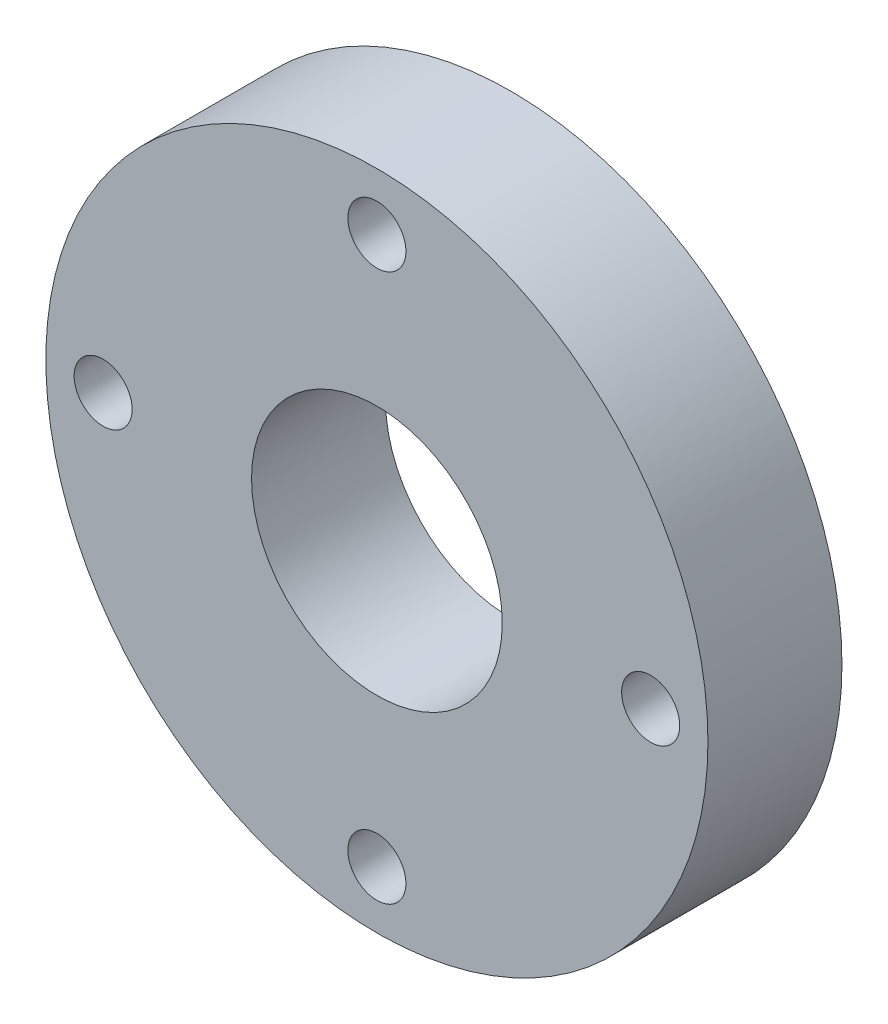
SolidWorks part; units mm, degrees
material "6061-T6 (SS)"
ref_plane "Front Plane" through (0, 0, 0) normal (0, 0, 1) x (1, 0, 0)
ref_plane "Top Plane" through (0, 0, 0) normal (0, 1, 0) x (1, 0, 0)
ref_plane "Right Plane" through (0, 0, 0) normal (1, 0, 0) x (0, 0, -1)
sketch "Sketch1" plane through (0, 0, 0) normal (1, 0, 0) x (0, 0, -1)
  line L0 (-95.847, -9.525) -> (-141.966, -9.525)
  line L5 (-1000, 0) -> (49000, 0)
  line L6 (0, -9.525) -> (0, 9.525)
  line L13 (0, 9.525) -> (-45.847, 9.525)
  line L26 (-45.847, 9.525) -> (-45.847, 12.7)
  line L27 (-45.847, 12.7) -> (-95.847, 12.7)
  line L32 (-95.847, 12.7) -> (-95.847, 9.525)
  line L34 (-160, 7) -> (-160, -7)
  line L36 (-95.847, -9.525) -> (-95.847, -12.7)
  line L37 (-95.847, -12.7) -> (-45.847, -12.7)
  line L38 (-45.847, -12.7) -> (-45.847, -9.525)
  line L39 (0, -9.525) -> (-45.847, -9.525)
  line L40 (-25.305, 37.6491) -> (-16.305, 37.6491)
  line L41 (-111.341, 22.6187) -> (-95.847, 22.6187)
  line L42 (-111.341, 22.6187) -> (-111.341, -22.6187)
  line L43 (-111.341, -22.6187) -> (-95.847, -22.6187)
  line L44 (-95.847, 22.6187) -> (-95.847, -22.6187)
  line L45 (-111.341, 22.6187) -> (-95.847, -22.6187) construction
  line L46 (-111.341, -22.6187) -> (-95.847, 22.6187) construction
  line L47 (-30.353, 22.6187) -> (-45.847, 22.6187)
  line L48 (-30.353, 22.6187) -> (-30.353, -22.6187)
  line L49 (-30.353, -22.6187) -> (-45.847, -22.6187)
  line L50 (-45.847, 22.6187) -> (-45.847, -22.6187)
  line L51 (-30.353, 22.6187) -> (-45.847, -22.6187) construction
  line L52 (-30.353, -22.6187) -> (-45.847, 22.6187) construction
  line L59 (-16.305, 37.6491) -> (-16.305, -37.6491)
  line L60 (-16.305, -37.6491) -> (-25.305, -37.6491)
  line L61 (-25.305, -22.6187) -> (-27.305, -22.6187)
  line L62 (-27.305, -22.6187) -> (-27.305, -12.5)
  line L63 (-27.305, -12.5) -> (-25.305, -12.5)
  line L64 (-25.305, -12.5) -> (-25.305, 12.5)
  line L65 (-25.305, 12.5) -> (-27.305, 12.5)
  line L66 (-27.305, 12.5) -> (-27.305, 22.6187)
  line L67 (-27.305, 22.6187) -> (-25.305, 22.6187)
  line L68 (-25.305, 22.6187) -> (-25.305, 37.6491)
  line L69 (-25.305, -22.6187) -> (-25.305, -37.6491)
  line L71 (-119.469, 37.6491) -> (-26.305, 37.6491)
  line L72 (-119.469, 37.6491) -> (-119.469, -37.6491)
  line L73 (-119.469, -37.6491) -> (-26.305, -37.6491)
  line L74 (-26.305, 37.6491) -> (-26.305, -37.6491)
  line L75 (-119.469, 37.6491) -> (-26.305, -37.6491) construction
  line L76 (-119.469, -37.6491) -> (-26.305, 37.6491) construction
  line L78 (-147.3, -7) -> (-160, -7)
  line L79 (-95.847, 9.525) -> (-141.966, 9.525)
  line L80 (-147.3, 7) -> (-160, 7)
  line L82 (-118.9065, 9.525) -> (-118.9065, -9.525) construction
  line L83 (-22.9235, 9.525) -> (-22.9235, -9.525) construction
  line L96 (-119.469, 37.6492) -> (-134.709, 37.6492)
  line L98 (-119.469, -37.6491) -> (-134.709, -37.6491)
  line L99 (-134.709, 37.6492) -> (-134.709, -37.6491)
  line L110 (-119.469, 37.6492) -> (-119.469, -37.6491)
  line L111 (-147.3, 7) -> (-147.3, 7.493)
  line L112 (-147.3, 7.493) -> (-141.966, 7.493)
  line L113 (-141.966, 7.493) -> (-141.966, 9.525)
  line L114 (-141.966, -9.525) -> (-141.966, -7.493)
  line L115 (-141.966, -7.493) -> (-147.3, -7.493)
  line L116 (-147.3, -7.493) -> (-147.3, -7)
  point P3 (0, 0)
  point P18 (-103.594, 0)
  point P24 (-38.1, 0)
  point P29 (-72.887, 0)
  point P48 (-16.305, 31.1339)
  point P70 (-134.709, 31.1339)
revolve "Main_body" add sketch "Sketch1" angle 360 about L5 region at (0, 23.5871, 127.089)
sketch "Sketch5" plane through (0, 0, 134.709) normal (0, 0, 1) x (1, 0, 0)
  circle A0 centre (0, 0) radius 14.2558
  dimension "D1" = 28.5115
extrude "seal_seat" cut sketch "Sketch5" against normal through all
hole_wizard "M6 Clearance Hole1" positions "Sketch3" profile "Sketch4" hole size "M6" standard "ANSI Metric" end condition through all
sketch "Sketch3" plane through (0, 0, 134.709) normal (0, 0, 1) x (1, 0, 0)
  point P0 (0, 31.1339)
sketch "Sketch4" plane through (0, 31.1339, 134.709) normal (1, 0, 0) x (0, -1, 0)
  line L0 (0, 0) -> (0, 15.24)
  line L1 (0, 15.24) -> (3.3, 15.24)
  line L2 (3.3, 15.24) -> (3.3, 0)
  line L5 (3.3, 0) -> (0, 0)
  line L11 (0, -6.35) -> (0, 107.95) construction
  dimension "Thru Hole Dia." = 6.6
  dimension "Thru Hole Depth" = 15.24
pattern_circular "CirPattern1" count 4 over 360 about axis through (0, 0, 1000) along (0, 0, -1) of "M6 Clearance Hole1"
